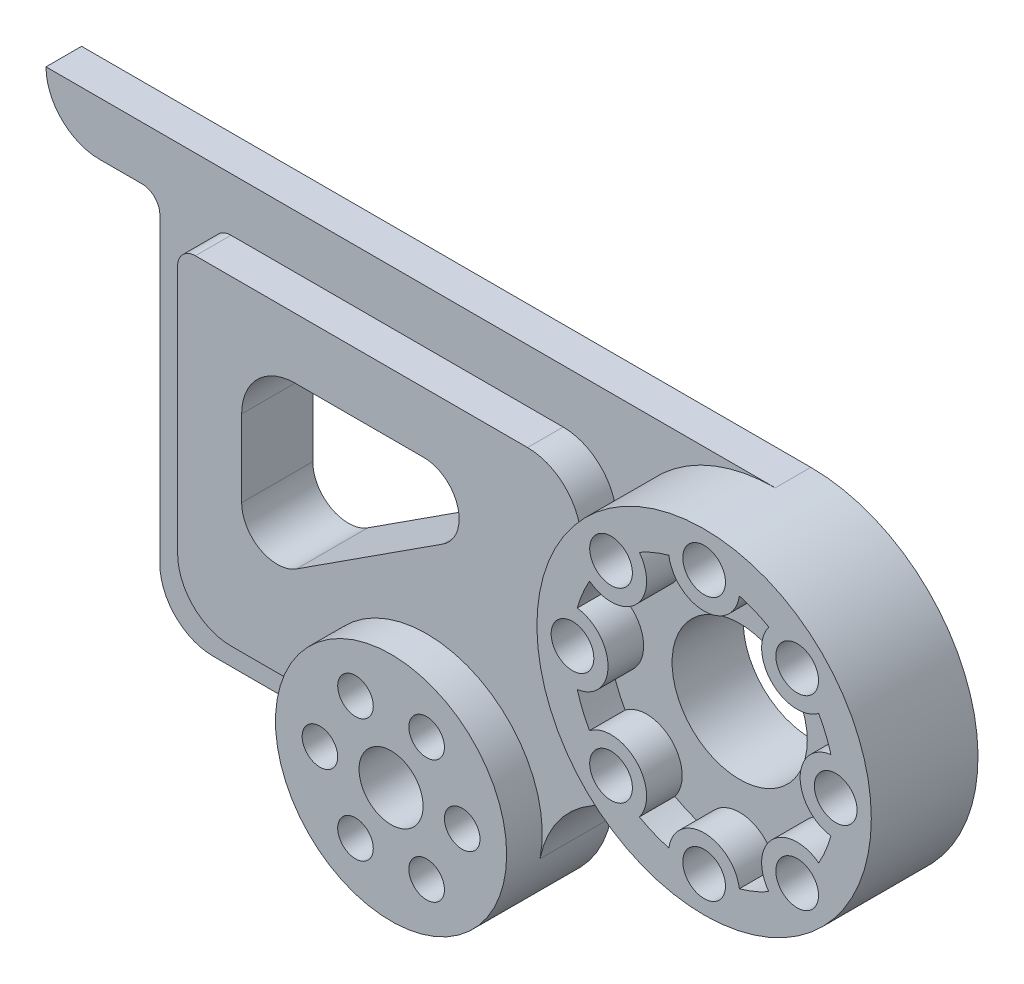
SolidWorks part; units mm, degrees
ref_plane "Спереди" through (0, 0, 0) normal (0, 0, 1) x (1, 0, 0)
ref_plane "Сверху" through (0, 0, 0) normal (0, 1, 0) x (1, 0, 0)
ref_plane "Справа" through (0, 0, 0) normal (1, 0, 0) x (0, 0, -1)
sketch "Эскиз1" plane through (0, 0, 0) normal (0, 0, 1) x (1, 0, 0)
  line L0 (0, 0) -> (0, 87.6337) construction
  line L1 (-88, -60) -> (-88, -1.8533) construction
  line L2 (-88, -60) -> (5.1435, -60) construction
  line L3 (0, 47) -> (-205, 47)
  line L4 (-190, 32) -> (-178, 32)
  line L5 (-173, 27) -> (-173, -58)
  line L6 (-153, 32) -> (-59.6238, 32)
  line L7 (-83.4297, -3.3957) -> (-124.5675, -30.0143)
  line L8 (-158, 27) -> (-158, -43)
  line L9 (-126.3699, -73) -> (-158, -73)
  line L10 (-143, -58) -> (-128.7707, -58)
  line L11 (-140, -21.6186) -> (-140, 0)
  line L12 (-125, 15) -> (-88.8622, 15)
  circle A0 centre (0, 0) radius 47
  arc A1 (-21.5903, 30.0476) -> (-30.0476, 21.5903) centre (0, 0) ccw
  circle A2 centre (0, 37) radius 6
  circle A3 centre (26.163, 26.163) radius 6
  circle A4 centre (37, 0) radius 6
  circle A5 centre (26.163, -26.163) radius 6
  circle A6 centre (0, -37) radius 6
  circle A7 centre (-26.163, -26.163) radius 6
  circle A8 centre (-37, 0) radius 6
  circle A9 centre (-26.163, 26.163) radius 6
  circle A10 centre (0, 0) radius 19
  arc A11 (-18.2012, 32.2136) -> (-32.2136, 18.2012) centre (-26.163, 26.163) cw
  arc A12 (-32.2136, 18.2012) -> (-35.6486, 9.9083) centre (0, 0) ccw
  arc A13 (9.9083, 35.6486) -> (-9.9083, 35.6486) centre (0, 37) cw
  arc A14 (32.2136, 18.2012) -> (18.2012, 32.2136) centre (26.163, 26.163) cw
  arc A15 (35.6486, -9.9083) -> (35.6486, 9.9083) centre (37, 0) cw
  arc A16 (18.2012, -32.2136) -> (32.2136, -18.2012) centre (26.163, -26.163) cw
  arc A17 (-9.9083, -35.6486) -> (9.9083, -35.6486) centre (0, -37) cw
  arc A18 (-32.2136, -18.2012) -> (-18.2012, -32.2136) centre (-26.163, -26.163) cw
  arc A19 (-35.6486, 9.9083) -> (-35.6486, -9.9083) centre (-37, 0) cw
  arc A20 (-35.6486, -9.9083) -> (-32.2136, -18.2012) centre (0, 0) ccw
  arc A21 (-18.2012, -32.2136) -> (-9.9083, -35.6486) centre (0, 0) ccw
  arc A22 (9.9083, -35.6486) -> (18.2012, -32.2136) centre (0, 0) ccw
  arc A23 (21.5903, -30.0476) -> (30.0476, -21.5903) centre (0, 0) ccw
  arc A24 (32.2136, -18.2012) -> (35.6486, -9.9083) centre (0, 0) ccw
  arc A25 (35.6486, 9.9083) -> (32.2136, 18.2012) centre (0, 0) ccw
  arc A26 (18.2012, 32.2136) -> (9.9083, 35.6486) centre (0, 0) ccw
  arc A27 (-9.9083, 35.6486) -> (-18.2012, 32.2136) centre (0, 0) ccw
  circle A28 centre (-88, -60) radius 32.5
  circle A29 centre (-88, -60) radius 9
  circle A30 centre (-68, -60) radius 5
  circle A31 centre (-78, -77.3205) radius 5
  circle A32 centre (-98, -77.3205) radius 5
  circle A33 centre (-108, -60) radius 5
  circle A34 centre (-98, -42.6795) radius 5
  circle A35 centre (-78, -42.6795) radius 5
  arc A36 (-16.3013, -44.0825) -> (-56.1273, -66.3546) centre (-26.7063, -72.2203) ccw
  arc A37 (-173, 27) -> (-178, 32) centre (-178, 27) ccw
  arc A38 (-153, 32) -> (-158, 27) centre (-153, 27) ccw
  arc A39 (-45.1987, 12.8871) -> (-59.6238, 32) centre (-59.6238, 17) ccw
  arc A40 (-173, -58) -> (-158, -73) centre (-158, -58) ccw
  arc A41 (-158, -43) -> (-143, -58) centre (-143, -43) ccw
  arc A42 (-114.2531, -79.1579) -> (-126.3699, -73) centre (-126.3699, -88) ccw
  arc A43 (-128.7707, -58) -> (-119.1776, -50.8235) centre (-128.7707, -48) ccw
  arc A44 (-205, 47) -> (-190, 32) centre (-190, 47) ccw
  arc A45 (-125, 15) -> (-140, 0) centre (-125, 0) ccw
  arc A46 (-124.5675, -30.0143) -> (-140, -21.6186) centre (-130, -21.6186) cw
  arc A47 (-88.8622, 15) -> (-83.4297, -3.3957) centre (-88.8622, 5) cw
  point P24 (0, 0)
  point P50 (0, 0)
  point P70 (-88, -60)
  point P80 (-173, 32)
  point P88 (-158, 32)
  point P91 (-173, -73)
  point P104 (-140, 15)
  point P107 (-140, -40)
  point P110 (-55, 15)
  dimension "D1" = 94
  dimension "D2" = 74
  dimension "D3" = 12
  dimension "D5" = 38
  dimension "D6" = 10
  dimension "D8" = 65
  dimension "D11" = 18
  dimension "D14" = 10
  dimension "D15" = 30
  dimension "D16" = 205
  dimension "D19" = 120
  dimension "D20" = 15
  dimension "D22" = 15
  dimension "D23" = 5
  dimension "D24" = 5
  dimension "D25" = 15
  dimension "D26" = 15
  dimension "D27" = 15
  dimension "D28" = 10
  dimension "D29" = 30
  dimension "D34" = 15
  dimension "D35" = 10
  dimension "D36" = 10
  dimension "D9" = 88
  dimension "D10" = 60
  dimension "D12" = 6
  dimension "D13" = 20
  dimension "D17" = 85
  dimension "D18" = 15
  dimension "D21" = 15
  dimension "D30" = 17
  dimension "D31" = 55
  dimension "D32" = 85
  dimension "D33" = 65
  dimension "D4" = 8
  dimension "D7" = 8
extrude "Бобышка-Вытянуть1" add sketch "Эскиз1" along normal blind 10 contours L3 A44 L4 A37 L5 A40 L9 A42 A28 A43 L10 A41 L8 A38 L6 A39 A0 region at (-29.7635, 39.4359, 0)
extrude "Бобышка-Вытянуть2" add sketch "Эскиз1<3>" along normal blind 20 contours L10 A43 A28 A36 A0 A39 L6 A38 L8 A41 L12 A47 L7 A46 L11 A45 region at (-43.4542, -22.0419, 0)
sketch "Эскиз1<3>" plane through (0, 0, 0) normal (0, 0, 1) x (1, 0, 0) same geometry as "Эскиз1"
extrude "Бобышка-Вытянуть3" add sketch "Эскиз1<4>" along normal blind 30 contours A28 A35 A34 A33 A32 A31 A30 A29 | A0 A27 A13 A26 A14 A25 A15 A24 A16 A22 A17 A21 A18 A20 A19 A12 A11 A9 A8 A7 A6 A5 A4 A3 A2 region at (32.294, 32.294, 0) region at (-81.2066, -90.8414, 0)
sketch "Эскиз1<4>" plane through (0, 0, 0) normal (0, 0, 1) x (1, 0, 0) same geometry as "Эскиз1"
extrude "Бобышка-Вытянуть4" add sketch "Эскиз1<5>" along normal blind 20 contours A13 A27 A11 A12 A19 A20 A18 A21 A17 A22 A16 A24 A15 A25 A14 A26 A10 region at (-13.7734, 33.252, 0)
sketch "Эскиз1<5>" plane through (0, 0, 0) normal (0, 0, 1) x (1, 0, 0) same geometry as "Эскиз1"
